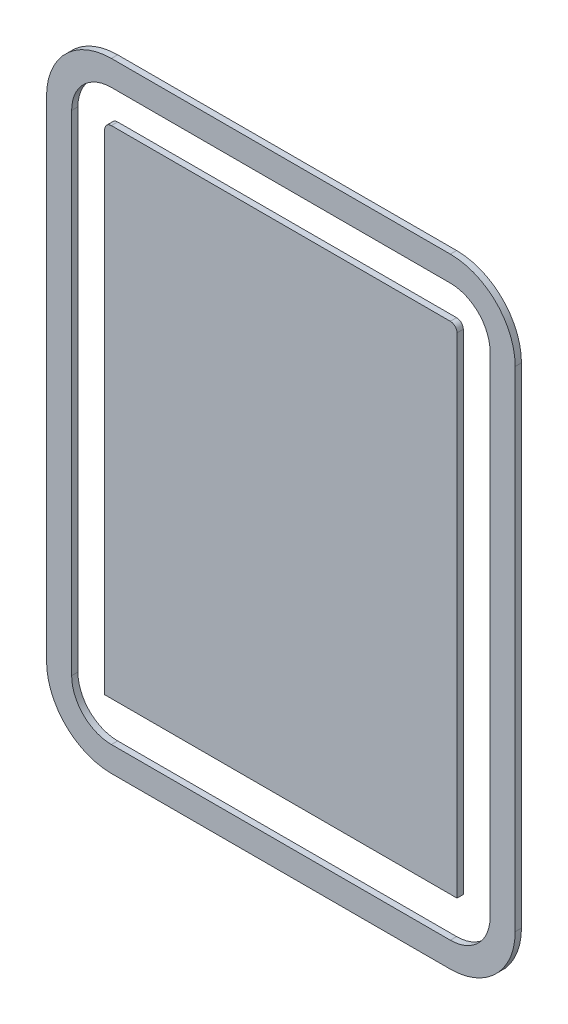
SolidWorks part; units mm, degrees
ref_plane "Front Plane" through (0, 0, 0) normal (0, 0, 1) x (1, 0, 0)
ref_plane "Top Plane" through (0, 0, 0) normal (0, 1, 0) x (1, 0, 0)
ref_plane "Right Plane" through (0, 0, 0) normal (1, 0, 0) x (0, 0, -1)
sketch "Sketch1" plane through (0, 0, 0) normal (0, 0, 1) x (1, 0, 0)
  line L8 (-61.5233, -81.5291) -> (22.6767, -81.5291)
  line L11 (22.6767, -81.5291) -> (22.6767, 35.4709)
  line L12 (-61.5233, 35.4709) -> (-61.5233, -81.5291)
  line L13 (21.0767, 37.0709) -> (-59.9233, 37.0709)
  line L14 (22.6767, -81.5291) -> (22.6767, 35.4709)
  line L15 (-61.5233, 35.4709) -> (-61.5233, -81.5291)
  line L16 (21.0767, 37.0709) -> (-59.9233, 37.0709)
  line L30 (30.5767, -81.5291) -> (30.5767, 35.4709)
  line L31 (-59.9233, -97.0291) -> (21.0767, -97.0291)
  line L32 (36.5767, -81.5291) -> (36.5767, 35.4709)
  line L33 (-75.4233, 35.4709) -> (-75.4233, -81.5291)
  line L34 (21.0767, 50.9709) -> (-59.9233, 50.9709)
  line L35 (-59.9233, -97.0291) -> (21.0767, -97.0291)
  line L36 (36.5767, -81.5291) -> (36.5767, 35.4709)
  line L37 (-75.4233, 35.4709) -> (-75.4233, -81.5291)
  line L38 (21.0767, 50.9709) -> (-59.9233, 50.9709)
  line L39 (-59.9233, -91.0291) -> (21.0767, -91.0291)
  line L40 (-69.4233, 35.4709) -> (-69.4233, -81.5291)
  line L41 (21.0767, 44.9709) -> (-59.9233, 44.9709)
  line L42 (30.5767, -81.5291) -> (30.5767, 35.4709)
  line L43 (-59.9233, -91.0291) -> (21.0767, -91.0291)
  line L44 (-69.4233, 35.4709) -> (-69.4233, -81.5291)
  line L45 (21.0767, 44.9709) -> (-59.9233, 44.9709)
  arc A9 (22.6767, 35.4709) -> (21.0767, 37.0709) centre (21.0767, 35.4709) ccw
  arc A10 (-59.9233, 37.0709) -> (-61.5233, 35.4709) centre (-59.9233, 35.4709) ccw
  arc A11 (22.6767, 35.4709) -> (21.0767, 37.0709) centre (21.0767, 35.4709) ccw
  arc A12 (-59.9233, 37.0709) -> (-61.5233, 35.4709) centre (-59.9233, 35.4709) ccw
  arc A20 (-75.4233, -81.5291) -> (-59.9233, -97.0291) centre (-59.9233, -81.5291) ccw
  arc A21 (21.0767, -97.0291) -> (36.5767, -81.5291) centre (21.0767, -81.5291) ccw
  arc A22 (36.5767, 35.4709) -> (21.0767, 50.9709) centre (21.0767, 35.4709) ccw
  arc A23 (-59.9233, 50.9709) -> (-75.4233, 35.4709) centre (-59.9233, 35.4709) ccw
  arc A24 (-75.4233, -81.5291) -> (-59.9233, -97.0291) centre (-59.9233, -81.5291) ccw
  arc A25 (21.0767, -97.0291) -> (36.5767, -81.5291) centre (21.0767, -81.5291) ccw
  arc A26 (36.5767, 35.4709) -> (21.0767, 50.9709) centre (21.0767, 35.4709) ccw
  arc A27 (-59.9233, 50.9709) -> (-75.4233, 35.4709) centre (-59.9233, 35.4709) ccw
  arc A28 (30.5767, 35.4709) -> (21.0767, 44.9709) centre (21.0767, 35.4709) ccw
  arc A29 (21.0767, -91.0291) -> (30.5767, -81.5291) centre (21.0767, -81.5291) ccw
  arc A30 (-69.4233, -81.5291) -> (-59.9233, -91.0291) centre (-59.9233, -81.5291) ccw
  arc A31 (-59.9233, 44.9709) -> (-69.4233, 35.4709) centre (-59.9233, 35.4709) ccw
  arc A32 (30.5767, 35.4709) -> (21.0767, 44.9709) centre (21.0767, 35.4709) ccw
  arc A33 (21.0767, -91.0291) -> (30.5767, -81.5291) centre (21.0767, -81.5291) ccw
  arc A34 (-69.4233, -81.5291) -> (-59.9233, -91.0291) centre (-59.9233, -81.5291) ccw
  arc A35 (-59.9233, 44.9709) -> (-69.4233, 35.4709) centre (-59.9233, 35.4709) ccw
  dimension "D1" = 8
  dimension "D2" = 2
  dimension "D3" = 3
extrude "Boss-Extrude1" add sketch "Sketch1" along normal blind 1.5 contours L38 A27 L37 A24 L35 A25 L36 A26 A35 L45 A32 L42 A33 L43 A34 L44 | A12 region at (-19.4233, -22.2356, 0) region at (-69.571, -91.1768, 0)
